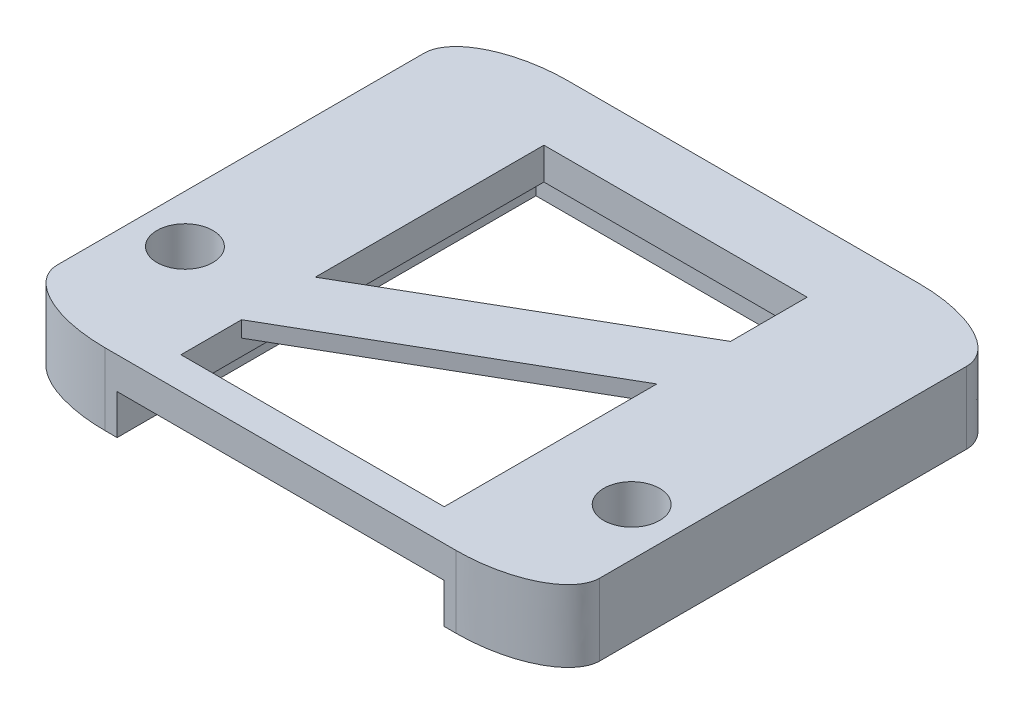
SolidWorks part; units mm, degrees
ref_plane "Front Plane" through (0, 0, 0) normal (0, 0, 1) x (1, 0, 0)
ref_plane "Top Plane" through (0, 0, 0) normal (0, 1, 0) x (1, 0, 0)
ref_plane "Right Plane" through (0, 0, 0) normal (1, 0, 0) x (0, 0, -1)
sketch "Sketch1" plane through (0, 0, 0) normal (0, 1, 0) x (1, 0, 0)
  line L0 (-10.25, 14.5) -> (-10.25, -14.5)
  line L1 (-17, -14.5) -> (17, -14.5)
  line L2 (-17, -14.5) -> (-17, 14.5)
  line L3 (-17, 14.5) -> (17, 14.5)
  line L4 (17, -14.5) -> (17, 14.5)
  line L5 (-17, -14.5) -> (17, 14.5) construction
  line L6 (-17, 14.5) -> (17, -14.5) construction
  line L7 (10.25, -14.5) -> (10.25, 14.5)
  line L8 (-17, 11.75) -> (17, 11.75)
  point P0 (0, 0)
  point P12 (-10, 14.5)
  point P13 (10, 14.5)
  dimension "D1" = 34
  dimension "D2" = 29
  dimension "D3" = 6.75
  dimension "D4" = 6.75
  dimension "D5" = 2.75
extrude "Boss-Extrude1" add sketch "Sketch1" along normal blind 2 contours L2 L1 L4 L3
extrude "Boss-Extrude2" add sketch "Sketch1<4>" against normal blind 2.5 contours L8 L2 L1 L0 | L8 L7 L1 L4 region at (-13.625, 0, 1.375) region at (13.625, 0, 1.375)
sketch "Sketch1<4>" plane through (0, 0, 0) normal (0, 1, 0) x (1, 0, 0) same geometry as "Sketch1"
sketch "Sketch2" plane through (0, 0, 0) normal (0, -1, 0) x (1, 0, 0)
  line L1 (17, -14.5) -> (-17, -14.5)
  line L2 (17, -14.5) -> (17, -11.75)
  line L3 (17, -11.75) -> (-17, -11.75)
  line L4 (-17, -14.5) -> (-17, -11.75)
extrude "Boss-Extrude7" add sketch "Sketch2" along normal blind 2.5
sketch "Sketch3" plane through (0, 0, 0) normal (0, -1, 0) x (1, 0, 0)
  line L0 (-8.25, -10.25) -> (8.25, -10.25)
  line L1 (8.25, -10.25) -> (8.25, 12.5)
  line L2 (8.25, 12.5) -> (-8.25, 12.5)
  line L3 (-8.25, 12.5) -> (-8.25, -10.25)
  line L4 (-10.25, -11.75) -> (10.25, -11.75)
  line L5 (10.25, -11.75) -> (10.25, 14.5)
  line L6 (10.25, 14.5) -> (-10.25, 14.5)
  line L7 (-10.25, 14.5) -> (-10.25, -11.75)
  line L8 (-10.25, -11.75) -> (10.25, -11.75) construction
  line L9 (10.25, -11.75) -> (10.25, 14.5) construction
  line L10 (10.25, 14.5) -> (-10.25, 14.5) construction
  line L11 (-10.25, 14.5) -> (-10.25, -11.75) construction
  line L12 (-8.25, 6.3881) -> (8.25, -3.1381) construction
  line L13 (-8.25, 4.0787) -> (8.25, -5.4475)
  line L14 (-8.25, 8.6975) -> (8.25, -0.8287)
  line L15 (-9.25, 4.6561) -> (7.25, -4.8702) construction
  line L16 (0, 1.625) -> (0, 12.5) construction
  point P23 (0, 3.9344)
  dimension "D3" = 60
  dimension "D5" = 2
  dimension "D6" = 10.875
  dimension "D2" = 2
  dimension "D7" = 2
  dimension "D8" = 1.5
  dimension "D9" = 2
  dimension "D1" = 0
  dimension "D4" = 2
extrude "Cut-Extrude1" cut sketch "Sketch3" against normal through all contours L3 L14 L1 L2 | L13 L3 L0 L1 region at (-1.3693, 0, -5.0719) region at (1.5292, 0, 7.7758)
sketch "Sketch4" plane through (0, -2.5, 0) normal (0, -1, 0) x (1, 0, 0)
  line L0 (14, 6.5) -> (-14, 6.5) construction
  line L1 (17, 14.5) -> (17, -14.5) construction
  line L2 (-17, 14.5) -> (-17, -14.5) construction
  line L4 (-17, 14.5) -> (17, 14.5) construction
  circle A0 centre (14, 6.5) radius 1.75
  circle A1 centre (-14, 6.5) radius 1.75
  point P4 (0, 0)
  dimension "D1" = 3.5
  dimension "D2" = 3
  dimension "D3" = 3
  dimension "D4" = 8
extrude "Cut-Extrude2" cut sketch "Sketch4" against normal through all
sketch "Sketch5" plane through (0, 0, 0) normal (0, -1, 0) x (1, 0, 0)
  line L1 (-8.25, 12.5) -> (8.25, 12.5)
  line L2 (-8.25, 12.5) -> (-8.25, -10.25)
  line L3 (-8.25, -10.25) -> (8.25, -10.25)
  line L4 (8.25, 12.5) -> (8.25, -10.25)
extrude "Cut-Extrude3" cut sketch "Sketch5" against normal blind 1
fillet "Fillet1" radius 6 4 edges at (-17, -0.25, 14.5) (17, -0.25, 14.5) (-17, -0.25, -14.5) (17, -0.25, -14.5) second distance 3 first distance on face at (0, -0.75, 14.5) first distance on face at (0, -0.25, -14.5)
